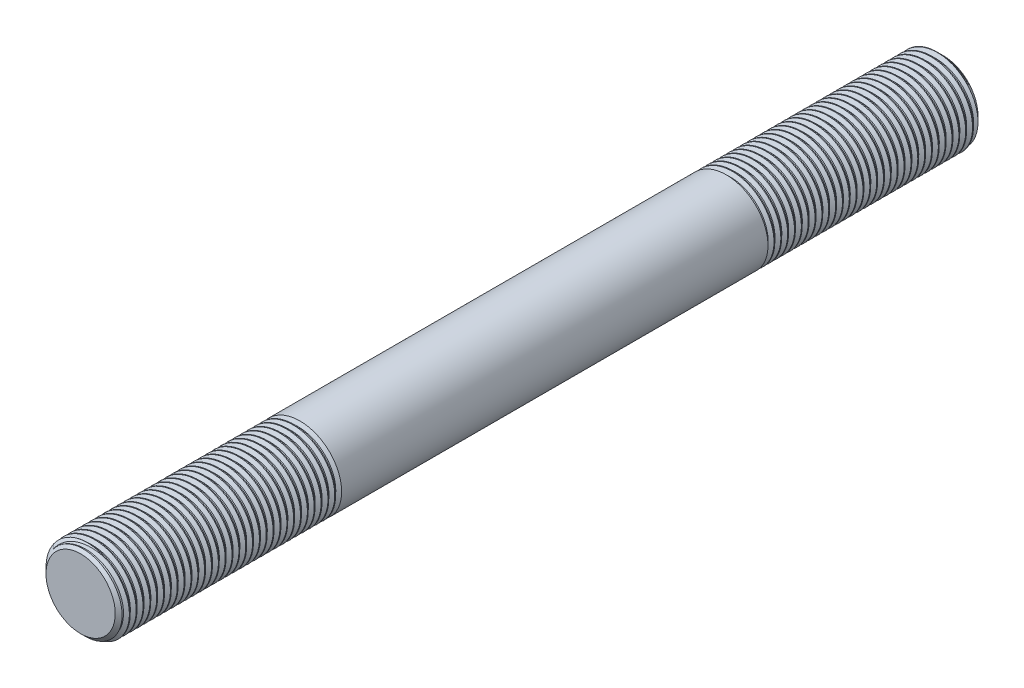
SolidWorks part; units mm, degrees
ref_plane "Front Plane" through (0, 0, 0) normal (0, 0, 1) x (1, 0, 0)
ref_plane "Top Plane" through (0, 0, 0) normal (0, 1, 0) x (1, 0, 0)
ref_plane "Right Plane" through (0, 0, 0) normal (1, 0, 0) x (0, 0, -1)
sketch "Sketch1" plane through (0, 0, 0) normal (0, 0, 1) x (1, 0, 0)
  circle A0 centre (0, 0) radius 9.525
  dimension "D1" = 19.05
extrude "Boss-Extrude1" add sketch "Sketch1" along normal mid plane 200
chamfer "Chamfer1" distance 1.5 angle 45 2 edges at (9.525, 0, -100) (9.525, 0, 100)
thread "Thread1" pitch 1.5875 profile "Thread Profile1" start angle 0, offset 2, length 52, pitch 1.5875, diameter 19.05
ref_plane "Plane1" through (-9.525, 0, 102) normal (0, -1, 0) x (-1, 0, 0)
sketch "Thread Profile1" plane through (-9.525, 0, 102) normal (0, -1, 0) x (-1, 0, 0)
  line L0 (0, 0) -> (0, 1.5875) construction
  line L11 (0, 0) -> (0, 1.3891)
  line L12 (0, 1.3891) -> (-0.8593, 0.893)
  line L13 (-0.8593, 0.893) -> (-0.8593, 0.4961)
  line L15 (-0.8593, 0.4961) -> (0, 0)
  line L17 (-0.8593, 0.6945) -> (0, 0.6945) construction
  point P2 (0, 0)
  dimension "Pitch" = 1.5875
  dimension "Profile_Angle" = 60
  dimension "Profile_Land" = 0.3969
  dimension "Profile_Height" = 0.8593
thread "Thread2" pitch 1.5875 profile "Thread Profile2" start angle 0, offset 2, length 52, pitch 1.5875, diameter 19.05
ref_plane "Plane2" through (9.525, 0, -102) normal (0, -1, 0) x (1, 0, 0)
sketch "Thread Profile2" plane through (9.525, 0, -102) normal (0, -1, 0) x (1, 0, 0)
  line L0 (0, 0) -> (0, 1.5875) construction
  line L11 (0, 0) -> (0, 1.3891)
  line L12 (0, 1.3891) -> (-0.8593, 0.893)
  line L13 (-0.8593, 0.893) -> (-0.8593, 0.4961)
  line L15 (-0.8593, 0.4961) -> (0, 0)
  line L17 (-0.8593, 0.6945) -> (0, 0.6945) construction
  point P2 (0, 0)
  dimension "Pitch" = 1.5875
  dimension "Profile_Angle" = 60
  dimension "Profile_Land" = 0.3969
  dimension "Profile_Height" = 0.8593
